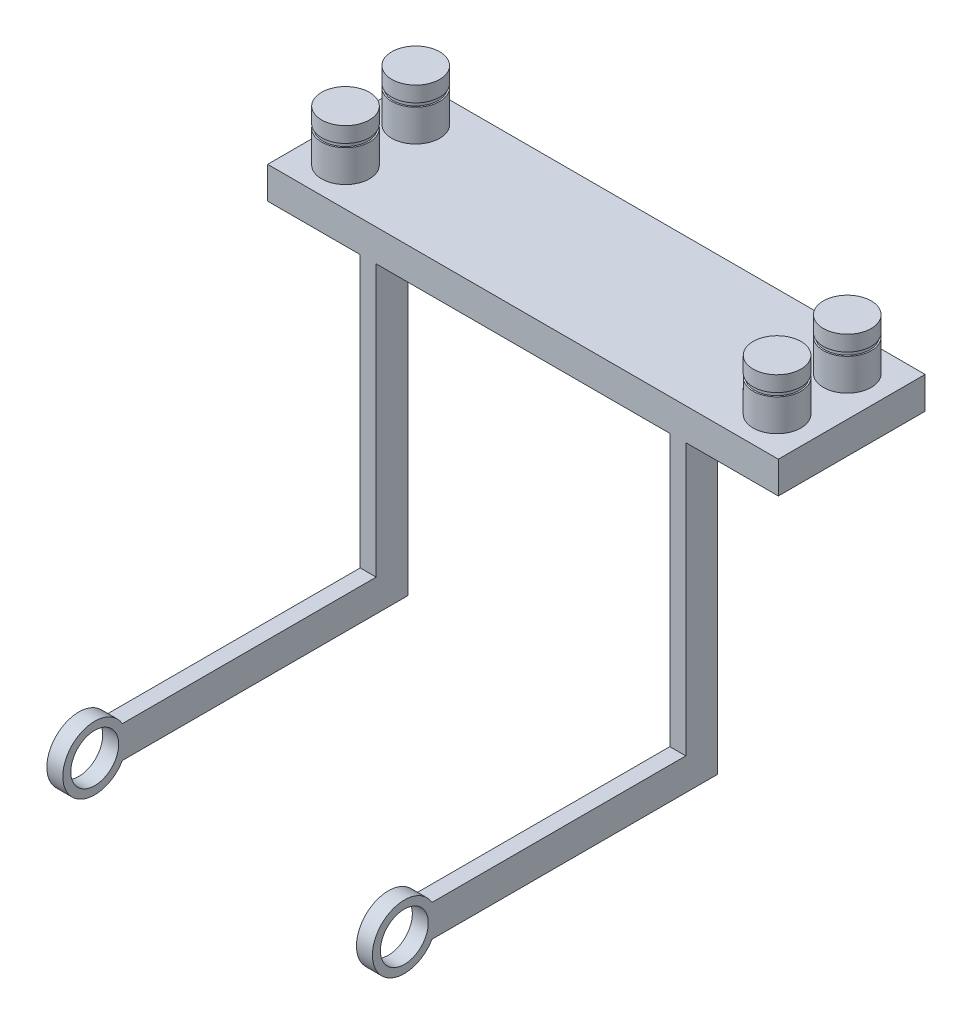
SolidWorks part; units mm, degrees
ref_plane "Front Plane" through (0, 0, 0) normal (0, 0, 1) x (1, 0, 0)
ref_plane "Top Plane" through (0, 0, 0) normal (0, 1, 0) x (1, 0, 0)
ref_plane "Right Plane" through (0, 0, 0) normal (1, 0, 0) x (0, 0, -1)
sketch "Sketch2" plane through (0, 0, 0) normal (0, 1, 0) x (1, 0, 0)
  line L1 (0, 0) -> (50.8, 0)
  line L2 (0, 0) -> (0, 29.21)
  line L3 (0, 29.21) -> (50.8, 29.21)
  line L4 (50.8, 0) -> (50.8, 29.21)
  dimension "D1" = 29.21
  dimension "D2" = 50.8
extrude "Boss-Extrude1" add sketch "Sketch2" along normal blind 6.35
sketch "Sketch4" plane through (0, 6.35, 0) normal (0, 1, 0) x (1, 0, 0)
  line L0 (0, 0) -> (50.8, 0) construction
  line L1 (50.8, 29.21) -> (0, 29.21) construction
  line L2 (50.8, 0) -> (50.8, 29.21) construction
  circle A0 centre (42.926, 7.62) radius 4.7625
  circle A1 centre (42.926, 21.59) radius 4.7625
  dimension "D1" = 9.525
  dimension "D2" = 9.525
  dimension "D3" = 7.62
  dimension "D4" = 7.62
  dimension "D5" = 7.874
  dimension "D6" = 7.874
extrude "Boss-Extrude2" add sketch "Sketch4" along normal blind 6.35
sketch "Sketch7" plane through (0, 12.7, 0) normal (0, 1, 0) x (1, 0, 0)
  line L0 (50.8, 29.21) -> (0, 29.21) construction
  line L1 (0, 0) -> (50.8, 0) construction
  line L2 (50.8, 0) -> (50.8, 29.21) construction
  circle A0 centre (42.926, 21.59) radius 4.4704
  circle A1 centre (42.926, 7.62) radius 4.4704
  dimension "D1" = 8.9408
  dimension "D2" = 8.9408
  dimension "D3" = 7.62
  dimension "D5" = 7.874
  dimension "D6" = 7.874
  dimension "D4" = 7.62
extrude "Boss-Extrude3" add sketch "Sketch7" along normal blind 0.7366
sketch "Sketch8" plane through (0, 13.4366, 0) normal (0, 1, 0) x (1, 0, 0)
  line L0 (50.8, 0) -> (50.8, 29.21) construction
  line L1 (50.8, 29.21) -> (0, 29.21) construction
  circle A0 centre (42.926, 21.59) radius 4.7625
  circle A1 centre (42.926, 7.62) radius 4.7625
  dimension "D1" = 9.525
  dimension "D2" = 9.525
  dimension "D3" = 7.874
  dimension "D4" = 7.62
extrude "Boss-Extrude4" add sketch "Sketch8" along normal blind 3.0734
sketch "Sketch11" plane through (0, 0, 0) normal (0, -1, 0) x (1, 0, 0)
  line L0 (0, -29.21) -> (0, 0) construction
  line L1 (29.21, 0) -> (32.385, 0)
  line L2 (29.21, 0) -> (29.21, -6.35)
  line L3 (29.21, -6.35) -> (32.385, -6.35)
  line L4 (32.385, 0) -> (32.385, -6.35)
  line L5 (0, 0) -> (50.8, 0) construction
  dimension "D1" = 6.35
  dimension "D2" = 3.175
  dimension "D3" = 29.21
  dimension "D4" = 0
extrude "Boss-Extrude5" add sketch "Sketch11" along normal blind 60.325
sketch "Sketch12" plane through (0, 0, 0) normal (0, 0, 1) x (1, 0, 0)
  line L0 (32.385, -60.325) -> (32.385, 0) construction
  line L1 (29.21, -60.325) -> (32.385, -60.325)
  line L2 (29.21, -60.325) -> (29.21, -53.975)
  line L3 (29.21, -53.975) -> (32.385, -53.975)
  line L4 (32.385, -60.325) -> (32.385, -53.975)
  dimension "D1" = 6.35
extrude "Boss-Extrude6" add sketch "Sketch12" along normal blind 55.991
sketch "Sketch13" plane through (29.21, 0, 0) normal (-1, 0, 0) x (0, 0, 1)
  line L0 (55.991, -53.975) -> (55.991, -60.325) construction
  circle A0 centre (55.991, -57.15) radius 6.35
  circle A1 centre (55.991, -57.15) radius 4.7625
  dimension "D1" = 12.7
  dimension "D2" = 9.525
extrude "Boss-Extrude8" add sketch "Sketch13" against normal blind 3.175
sketch "Sketch17" plane through (29.21, 0, 0) normal (-1, 0, 0) x (0, 0, 1)
  line L0 (55.991, -53.975) -> (55.991, -60.325) construction
  circle A0 centre (55.991, -57.15) radius 4.7625
  dimension "D1" = 9.525
extrude "Cut-Extrude3" cut sketch "Sketch17" against normal blind 3.175
mirror "Mirror3" about plane through (0, 0, 0) normal (1, 0, 0) of "Boss-Extrude1", "Boss-Extrude2", "Boss-Extrude3", "Boss-Extrude4", "Boss-Extrude5", "Boss-Extrude6", "Boss-Extrude8", "Cut-Extrude3"
